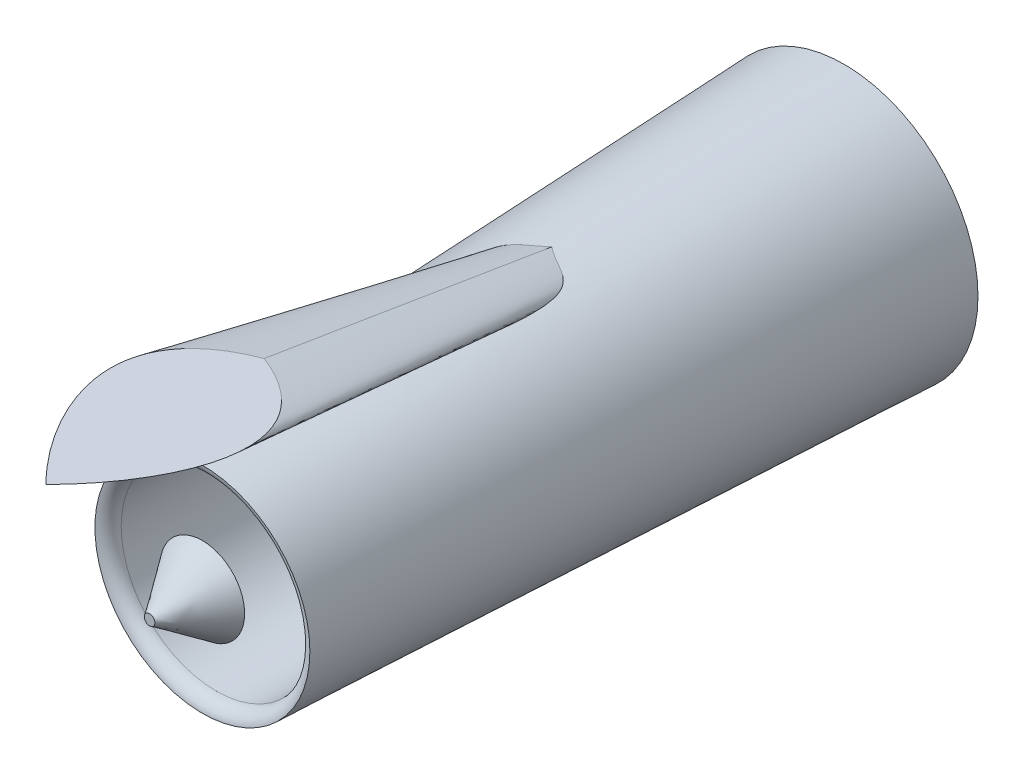
SolidWorks part; units mm, degrees
ref_plane "Front Plane" through (0, 0, 0) normal (0, 0, 1) x (1, 0, 0)
ref_plane "Top Plane" through (0, 0, 0) normal (0, 1, 0) x (1, 0, 0)
ref_plane "Right Plane" through (0, 0, 0) normal (1, 0, 0) x (0, 0, -1)
sketch "Sketch2" plane through (0, 0, 0) normal (0, 1, 0) x (1, 0, 0)
  line L0 (0, -5194.446) -> (0, 1731.482)
  line L1 (0, 0) -> (-18096.1342, 0) construction
  line L2 (0, 0) -> (-22098, -13277.818) construction
  line L3 (-22098, -15095.8741) -> (-22098, -12671.7993)
  line L4 (-22098, -12671.7993) -> (0, 1731.482)
  line L5 (-22098, -15095.8741) -> (0, -5194.446)
  line L6 (-9275.7037, -4314.3398) -> (-9275.7037, -5573.4051) construction
  line L7 (-9275.7037, -5573.4051) -> (-9275.7037, -9350.601) construction
  line L8 (-9275.7037, -5573.4051) -> (0, -5573.4051) construction
  line L9 (0, 346.2964) -> (-6827.52, -3825.6374)
  line L10 (0, -29565.6) -> (-7316.724, -34881.5112) construction
  line L11 (0, -29565.6) -> (-8167.6786, -29565.6) construction
  line L12 (0, -28507.0982) -> (0, -32741.1055)
  line L13 (-7316.724, -35992.9378) -> (-7316.724, -34511.0356)
  line L14 (-7316.724, -34511.0356) -> (0, -28507.0982)
  line L15 (0, -32741.1055) -> (-7316.724, -35992.9378)
  line L16 (-2399.2704, -30475.8849) -> (-2399.2704, -31308.772) construction
  line L17 (-2399.2704, -31308.772) -> (-2399.2704, -33807.4331) construction
  line L18 (-2399.2704, -31308.772) -> (0, -31308.772) construction
  line L19 (-6827.52, -3825.6374) -> (-6827.52, -6593.1427)
  line L20 (-6827.52, -6593.1427) -> (0, -3116.6676)
  line L21 (0, 346.2964) -> (0, -3116.6676) construction
  line L22 (0, -3116.6676) -> (0, 346.2964) construction
  line L23 (0, 346.2964) -> (0, -1385.1856) construction
  line L24 (0, 346.2964) -> (0, -3116.6676) construction
  line L25 (0, -1385.1856) -> (-6827.52, -5209.39) construction
  line L26 (0, 346.2964) -> (-22098, -13156.6142) construction
  line L27 (-3160.776, -1585.0854) -> (-3160.776, -3155.5874) construction
  line L28 (-3160.776, -3155.5874) -> (-3160.776, -4726.0893) construction
  line L29 (-3160.776, -3155.5874) -> (0, -3155.5874) construction
  dimension "Wing Sweep" = 31
  dimension "Half Span" = 22098
  dimension "Wing Root" = 6925.928
  dimension "D4" = 1731.482
  dimension "Wing Tip" = 2424.0748
  dimension "D6" = 606.0187
  dimension "Wing YBar" = 9275.7037
  dimension "Tail Sweep" = 36
  dimension "Tail Root" = 4234.0073
  dimension "D10" = 1058.5018
  dimension "Tail Tip" = 1481.9022
  dimension "D12" = 370.4756
  dimension "D13" = 7316.724
  dimension "Tail Ybar" = 2399.2704
  dimension "First Spar" = 1385.1856
  dimension "Second Spar" = 4848.1496
  dimension "Fuel Tip" = 2767.5053
  dimension "Tip Spar" = 484.815
  dimension "Fuel Ybar" = 3160.776
  dimension "Fuel Tank Length" = 6827.52
  dimension "Tail Arm" = 29565.6
sketch "Sketch4" plane through (0, 0, 0) normal (0, 1, 0) x (1, 0, 0)
  line L0 (0, 15244.4349) -> (0, -37790.7651) construction
  line L1 (-2240.28, 15244.4349) -> (2240.28, 15244.4349) construction
  line L2 (-2240.28, 8523.5949) -> (-2240.28, -28829.6451)
  line L3 (-2240.28, -37790.7651) -> (2240.28, -37790.7651) construction
  line L4 (2240.28, 8523.5949) -> (2240.28, -28829.6451)
  line L5 (0, -5194.446) -> (0, 1731.482) construction
  line L6 (-9275.7037, -5573.4051) -> (0, -5573.4051) construction
  line L7 (-2399.2704, -31308.772) -> (0, -31308.772) construction
  line L8 (0, 0) -> (-22098, -13277.818) construction
  line L9 (-22098, -12671.7993) -> (0, 1731.482) construction
  line L10 (-8451.85, 1616.4392) -> (-6132.83, 1616.4392)
  line L11 (-8451.85, 1616.4392) -> (-8451.85, -3941.0808)
  line L12 (-8451.85, -3941.0808) -> (-6132.83, -3941.0808)
  line L13 (-6132.83, 1616.4392) -> (-6132.83, -3941.0808)
  line L14 (2240.28, 8523.5949) -> (-2240.28, 8523.5949)
  arc A0 (-2240.28, -28829.6451) -> (2240.28, -28829.6451) centre (0, -28829.6451) ccw construction
  spline S0 degree 2 poles (-2240.28, 8523.5949) (-3493.3317, 12850.6725) (0, 15244.4349) knots 0 0 0 1 1 1 construction
  spline S1 degree 2 poles (2240.28, 8523.5949) (3493.3317, 12850.6725) (0, 15244.4349) knots 0 0 0 1 1 1 construction
  spline S2 degree 3 poles (-2240.28, -28829.6451) (-2085.9319, -24596.8954) (-2150.7047, -30572.2669) (-921.2874, -32754.607) (0, -32741.1055) knots 0 0 0 0 0.731427 1 1 1 1 construction
  spline S3 degree 3 poles (2240.28, -28829.6451) (2085.9319, -24596.8954) (2150.7047, -30572.2669) (921.2874, -32754.607) (0, -32741.1055) knots 0 0 0 0 0.731427 1 1 1 1 construction
  spline S4 degree 2 poles (-2240.28, -28829.6451) (-2598.9168, -25444.3223) (0, -27753.3552) knots 0 0 0 1 1 1
  spline S5 degree 2 poles (2240.28, -28829.6451) (2598.9168, -25444.3223) (0, -27753.3552) knots 0 0 0 1 1 1
  point P6 (0, 8523.5949)
  point P7 (0, -28829.6451)
  point P8 (0, -5573.4051)
  point P15 (0, -31069.9251)
  point P28 (-7292.34, 1616.4392)
  point P29 (-7292.34, -3021.6008)
  point P35 (-7292.34, -4381.6799)
  point P44 (-7292.34, -606.5688)
  dimension "Fuse Length" = 53035.2
  dimension "Fuse Dia" = 4480.56
  dimension "D3" = 6720.84
  dimension "D4" = 8961.12
  dimension "D6" = 7292.34
  dimension "Engine Dia" = 2319.02
  dimension "Engine Length" = 5557.52
  dimension "D9" = 4638.04
  dimension "D10" = 2223.008
  dimension "D11" = 4966.8362
  dimension "D2" = 20817.84
ref_plane "Plane1" through (0, 609.6, 0) normal (0, 1, 0) x (1, 0, 0)
sketch "Sketch10" plane through (0, 0, 0) normal (0, 1, 0) x (1, 0, 0)
  line L0 (-22098, -12671.7993) -> (-2240.28, 271.2873)
  line L1 (-2240.28, 8523.5949) -> (-2240.28, -28829.6451) construction
  line L2 (-22098, -12671.7993) -> (-22098, -15095.8741)
  line L3 (-22098, -15095.8741) -> (-7292.34, -8461.9172)
  line L4 (-7292.34, -8461.9172) -> (-2240.28, -8461.9172)
  line L5 (-22098, -15095.8741) -> (0, -5194.446) construction
  line L6 (-22098, -12671.7993) -> (0, 1731.482) construction
  line L7 (-2240.28, -8461.9172) -> (-2240.28, 271.2873) construction
  line L9 (0, 271.2873) -> (0, -8461.9172)
  line L10 (0, -8461.9172) -> (-2240.28, -8461.9172)
  line L11 (0, -5194.446) -> (0, 1731.482) construction
  line L12 (-2240.28, 271.2873) -> (0, 1731.482)
  line L13 (0, 1731.482) -> (0, 271.2873)
ref_plane "Plane4" through (13979.3336, 0, 17035.9747) normal (0.6343, 0, 0.773) x (0.773, 0, -0.6343)
ref_plane "Plane2" through (-7316.724, 0, 0) normal (1, 0, 0) x (0, 0, -1)
ref_plane "Plane5" through (0, 0, -1616.4392) normal (0, 0, 1) x (1, 0, 0)
ref_plane "Plane6" through (0, 0, 3941.0808) normal (0, 0, 1) x (1, 0, 0)
ref_plane "Plane7" through (-7292.34, 0, 0) normal (1, 0, 0) x (0, 0, -1)
sketch "Sketch13" plane through (0, 0, -1616.4392) normal (0, 0, 1) x (1, 0, 0)
  line L1 (-8451.85, 0) -> (-6132.83, 0) construction
  line L2 (-7292.34, 0) -> (-6132.83, 0) construction
  line L3 (-7292.34, 0) -> (-7292.34, -1159.51) construction
  circle A0 centre (-7292.34, 0) radius 1159.51
sketch "Sketch14" plane through (0, 0, 3941.0808) normal (0, 0, 1) x (1, 0, 0)
  line L0 (-8451.85, 0) -> (-6132.83, 0) construction
  line L1 (-7292.34, 0) -> (-6361.43, 0) construction
  line L2 (-7292.34, 0) -> (-7292.34, -930.91) construction
  line L3 (-7292.34, 0) -> (-7249.9946, 929.9464) construction
  circle A0 centre (-7292.34, 0) radius 930.91
  point P2 (-7190.2668, 925.297)
  dimension "D1" = 228.6
sketch "Sketch15" plane through (-7292.34, 0, 0) normal (1, 0, 0) x (0, 0, -1)
  line L0 (1616.4392, 0) -> (-3941.0808, 0) construction
  line L1 (1616.4392, 0) -> (-3941.0808, 0) construction
  line L2 (1616.4392, 0) -> (1616.4392, -1159.51) construction
  line L3 (-3941.0808, 0) -> (-3941.0808, -930.91) construction
  line L6 (1616.4392, -1159.51) -> (-3941.0808, -930.91) construction
  line L7 (1616.4392, -1159.51) -> (-5492.1559, -1159.51) construction
  spline S0 degree 2 poles (1616.4392, -1159.51) (-1167.6686, -1217.6329) (-3941.0808, -930.91) knots 0 0 0 1 1 1
loft "Loft2" add profiles "Sketch13", "Sketch14" connector at (-6132.83, 0, -1616.4392) connector at (-6361.43, 0, 3941.0808)
sketch "Sketch16" plane through (0, 0, -1616.4392) normal (0, 0, -1) x (-1, 0, 0)
  circle A0 centre (7292.34, 0) radius 824.23
  circle A1 centre (7292.34, 0) radius 1159.51 construction
  circle A2 centre (7292.34, 0) radius 930.91 construction
  dimension "D1" = 106.68
extrude "Cut-Extrude1" cut sketch "Sketch16" against normal through all both and the other way through all
fillet "Fillet1" radius 304.8 1 edges at (-6468.11, 0, -1616.4392)
fillet "Fillet2" radius 121.92 1 edges at (-6468.11, 0, 3941.0808)
ref_plane "Plane8" through (0, 929.9464, 0) normal (0, 1, 0) x (1, 0, 0)
sketch "Sketch17" plane through (0, 929.9464, 0) normal (0, 1, 0) x (1, 0, 0)
  line L0 (-7292.34, 1616.4392) -> (-7292.34, -3941.0808) construction
  line L1 (-8451.85, 1616.4392) -> (-6132.83, 1616.4392) construction
  line L2 (-8451.85, -3941.0808) -> (-6132.83, -3941.0808) construction
  spline S0 degree 3 poles (-7292.34, -149.3688) (-6646.0952, -977.1535) (-7181.4944, -1981.2715) (-7292.34, -2877.7155) knots 0 0 0 0 1 1 1 1
  spline S1 degree 3 poles (-7292.34, -149.3688) (-7938.5848, -977.1535) (-7403.1856, -1981.2715) (-7292.34, -2877.7155) knots 0 0 0 0 1 1 1 1
  dimension "D1" = 457.2
sketch "Sketch18" plane through (0, 0, 3941.0808) normal (0, 0, 1) x (1, 0, 0)
  circle A0 centre (-7292.34, 0) radius 365.76
  dimension "D1" = 731.52
ref_plane "Plane9" through (0, 0, 4398.2808) normal (0, 0, 1) x (1, 0, 0)
sketch "Sketch19" plane through (0, 0, 4398.2808) normal (0, 0, 1) x (1, 0, 0)
  circle A0 centre (-7292.34, 0) radius 45.72
  dimension "D1" = 91.44
loft "Loft3" add profiles "Sketch19", "Sketch18" connector at (-7325.9035, 31.0453, 4398.2808) connector at (-7425.7022, 340.5802, 3941.0808)
ref_plane "Plane10" through (0, 1463.3464, 0) normal (0, 1, 0) x (1, 0, 0)
sketch "Sketch20" plane through (0, 1463.3464, 0) normal (0, 1, 0) x (1, 0, 0)
  line L0 (-7292.34, -3406.1504) -> (-7292.34, -5295.5283) construction
  line L1 (-7292.34, 1616.4392) -> (-7292.34, -3941.0808) construction
  spline S0 degree 3 poles (-7292.34, -3406.1504) (-6242.025, -3812.9933) (-6806.4277, -4813.3352) (-7292.34, -5295.5283) knots 0 0 0 0 1 1 1 1
  spline S1 degree 3 poles (-7292.34, -3406.1504) (-8342.655, -3812.9933) (-7778.2523, -4813.3352) (-7292.34, -5295.5283) knots 0 0 0 0 1 1 1 1
loft "Loft4" add profiles "Sketch20", "Sketch17" connector at (-7292.34, 1463.3464, 3406.1504) connector at (-7292.34, 929.9464, 149.3688)
ref_plane "Plane11" through (0, 548.9464, 0) normal (0, 1, 0) x (1, 0, 0)
sketch "Sketch21" plane through (0, 548.9464, 0) normal (0, 1, 0) x (1, 0, 0)
  line L0 (-6132.83, 1616.4392) -> (-6132.83, -3941.0808) construction
  line L1 (-6132.83, 1616.4392) -> (-8451.85, 1616.4392)
  line L2 (-6132.83, 1616.4392) -> (-6132.83, -3941.0808)
  line L3 (-6132.83, -3941.0808) -> (-8451.85, -3941.0808)
  line L4 (-8451.85, 1616.4392) -> (-8451.85, -3941.0808)
  line L5 (-8451.85, 1616.4392) -> (-8451.85, -3941.0808) construction
  line L6 (-8451.85, -3941.0808) -> (-6132.83, -3941.0808) construction
  dimension "D2" = 0
equation "\"D6@Sketch2\" = \"Wing Tip@Sketch2\" / 4"
equation "\"D4@Sketch2\" = \"Wing Root@Sketch2\" / 4"
equation "\"D10@Sketch2\" = \"Tail Root@Sketch2\" / 4"
equation "\"D12@Sketch2\" = \"Tail Tip@Sketch2\" / 4"
equation "\"D13@Sketch2\"=48.01/2"
equation "\"First Spar@Sketch2\"=0.2 * \"Wing Root@Sketch2\""
equation "\"Second Spar@Sketch2\"   = 0.7 * \"Wing Root@Sketch2\""
equation "\"Tip Spar@Sketch2\"=0.2 * \"Wing Tip@Sketch2\""
equation "\"D3@Sketch4\" = 1.5 * \"Fuse Dia@Sketch4\""
equation "\"D4@Sketch4\" = 2 * \"Fuse Dia@Sketch4\""
equation "\"D6@Sketch4\" = 0.33 * \"Half Span@Sketch2\""
equation "\"D9@Sketch4\" = 2 * \"Engine Dia@Sketch4\""
equation "\"D10@Sketch4\" = 0.40 * \"Engine Length@Sketch4\""
